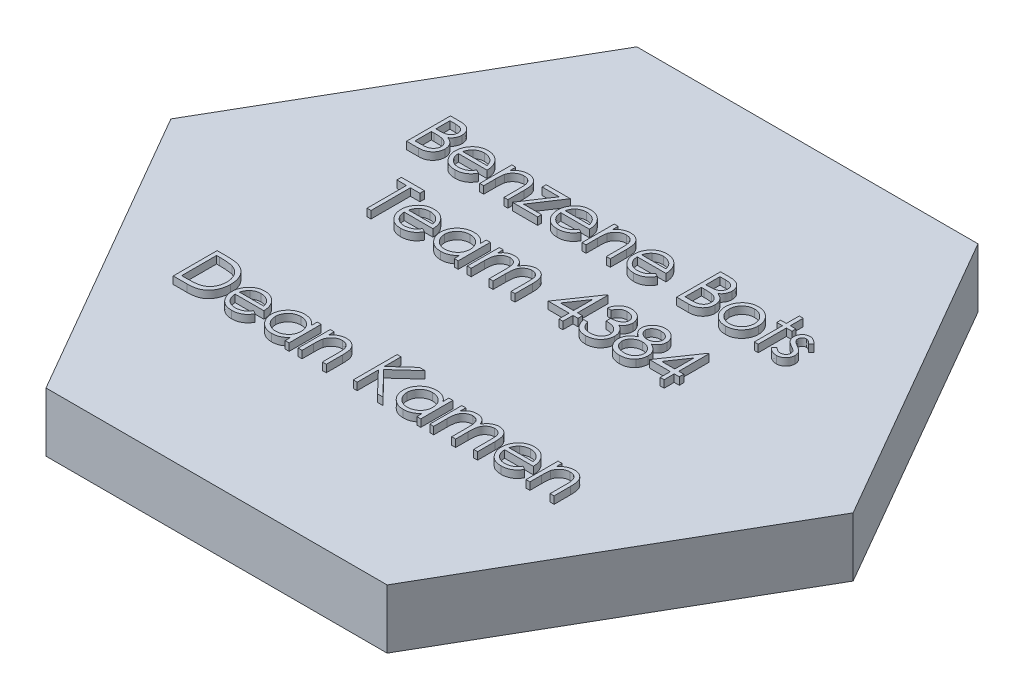
SolidWorks part; units mm, degrees
ref_plane "Front Plane" through (0, 0, 0) normal (0, 0, 1) x (1, 0, 0)
ref_plane "Top Plane" through (0, 0, 0) normal (0, 1, 0) x (1, 0, 0)
ref_plane "Right Plane" through (0, 0, 0) normal (1, 0, 0) x (0, 0, -1)
sketch "Sketch1" plane through (0, 0, 0) normal (0, 1, 0) x (1, 0, 0)
  line L1 (73.3235, 0) -> (36.6617, 63.5)
  line L2 (36.6617, 63.5) -> (-36.6617, 63.5)
  line L3 (-36.6617, 63.5) -> (-73.3235, 0)
  line L4 (-73.3235, 0) -> (-36.6617, -63.5)
  line L5 (-36.6617, -63.5) -> (36.6617, -63.5)
  line L6 (36.6617, -63.5) -> (73.3235, 0)
  circle A0 centre (0, 0) radius 63.5 construction
  dimension "D1" = 127
extrude "Boss-Extrude1" add sketch "Sketch1" along normal blind 12.7
sketch "Sketch3" plane through (0, 0, 0) normal (0, 1, 0) x (1, 0, 0)
  line L1 (34.8287, -60.325) -> (69.6573, 0)
  line L2 (69.6573, 0) -> (34.8287, 60.325)
  line L3 (34.8287, 60.325) -> (-34.8287, 60.325)
  line L4 (-34.8287, 60.325) -> (-69.6573, 0)
  line L5 (-69.6573, 0) -> (-34.8287, -60.325)
  line L6 (-34.8287, -60.325) -> (34.8287, -60.325)
  circle A0 centre (0, 0) radius 60.325 construction
  point P1 (-65.1126, -2.7272)
  point P10 (0, 0)
  point P11 (-69.6573, 0)
  dimension "D1" = 120.65
extrude "Cut-Extrude1" cut sketch "Sketch3" along normal blind 3.81
sketch "Sketch4" plane through (0, 0, 0) normal (0, 1, 0) x (1, 0, 0)
  text T0 "Benzene Bots\r\n  Team 4384\r\n\r\nDean Kamen\r\n" font "Century Gothic" height in points 36
extrude "Boss-Extrude2" add sketch "Sketch4" along normal offset from surface (14.2875 mm away) 1.5875 up to face at (0, 12.7, 0) offset beyond the face yes
extrude "Cut-Extrude2" cut sketch "Sketch4<2>" along normal blind 3.81
sketch "Sketch4<2>" plane through (0, 0, 0) normal (0, 1, 0) x (1, 0, 0) same geometry as "Sketch4"
